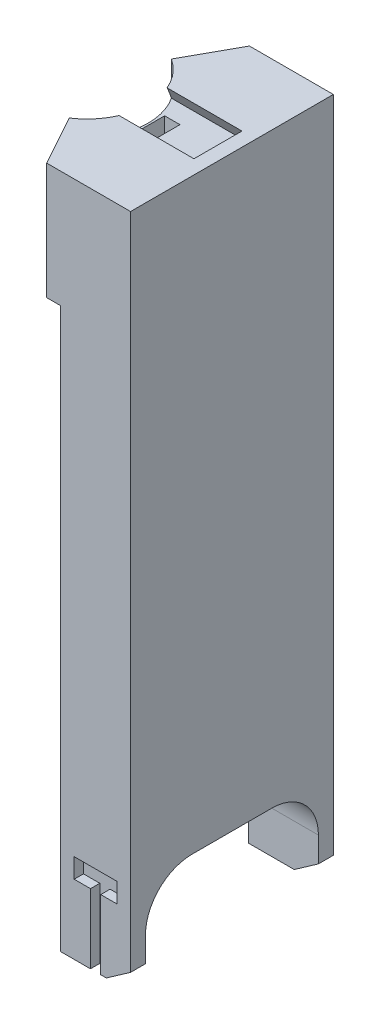
SolidWorks part; units mm, degrees
ref_plane "Front Plane" through (0, 0, 0) normal (0, 0, 1) x (1, 0, 0)
ref_plane "Top Plane" through (0, 0, 0) normal (0, 1, 0) x (1, 0, 0)
ref_plane "Right Plane" through (0, 0, 0) normal (1, 0, 0) x (0, 0, -1)
sketch "Sketch2" plane through (0, 0, 0) normal (0, 1, 0) x (1, 0, 0)
  line L0 (-9, 21.75) -> (-14.9513, 10.9504)
  line L1 (-9, -21.75) -> (9, -21.75)
  line L2 (-9, -21.75) -> (-9, 21.75)
  line L3 (-9, 21.75) -> (9, 21.75)
  line L4 (9, -21.75) -> (9, 21.75)
  line L5 (-9, -21.75) -> (9, 21.75) construction
  line L6 (-9, 21.75) -> (9, -21.75) construction
  line L7 (-9, -21.75) -> (-14.9513, -10.9504)
  circle A0 centre (-22.05, 0) radius 13.05
  point P0 (0, 0)
  dimension "D1" = 26.1
  dimension "D2" = 43.5
  dimension "D3" = 18
extrude "Boss-Extrude1" add sketch "Sketch2" along normal blind 25 contours A0 L2 L0 | A0 L7 L2 | L1 L4 L3 L2 region at (-10.8717, 0, -12.2283) region at (0, 0, 0) region at (-10.8717, 0, 12.2283)
ref_plane "Plane1" through (-9, 0, 0) normal (1, 0, 0) x (0, 0, -1)
sketch "Sketch3" plane through (-9, 0, 0) normal (1, 0, 0) x (0, 0, -1)
  line L0 (-5.15, 25) -> (5.15, 25)
  line L1 (5.15, 25) -> (7.15, 21.5359)
  line L2 (7.15, 21.5359) -> (-7.15, 21.5359)
  line L3 (-7.15, 21.5359) -> (-5.15, 25)
  line L4 (-21.75, 25) -> (21.75, 25) construction
  point P4 (0, 25)
  point P7 (0, 25)
  point P8 (0, 21.5359)
  dimension "D1" = 10.3
  dimension "D2" = 14.3
  dimension "D3" = 60
extrude "Cut-Extrude1" cut sketch "Sketch3" against normal through all and the other way blind 15
sketch "Sketch4" plane through (-9, 0, 0) normal (1, 0, 0) x (0, 0, -1)
  line L0 (0, 29.4041) -> (0, 4.5359) construction
  line L1 (3.15, 29.4041) -> (3.15, 4.5359)
  line L2 (-3.15, 29.4041) -> (-3.15, 4.5359)
  line L3 (7.15, 21.5359) -> (-7.15, 21.5359) construction
  arc A0 (3.15, 29.4041) -> (-3.15, 29.4041) centre (0, 29.4041) ccw
  arc A1 (-3.15, 4.5359) -> (3.15, 4.5359) centre (0, 4.5359) ccw
  point P3 (0, 16.97)
  dimension "D1" = 6.3
  dimension "D2" = 17
extrude "Cut-Extrude2" cut sketch "Sketch4" along normal blind 3.3 from offset 0.4
sketch "Sketch5" plane through (0, 0, 0) normal (0, -1, 0) x (1, 0, 0)
  line L0 (-9, -21.75) -> (9, -21.75) construction
  line L1 (9, 21.75) -> (-6, 21.75)
  line L2 (9, 21.75) -> (9, -21.75)
  line L3 (9, -21.75) -> (-6, -21.75)
  line L4 (-6, 21.75) -> (-6, -21.75)
  dimension "D1" = 15
extrude "Boss-Extrude2" add sketch "Sketch5" along normal blind 120
sketch "Sketch6" plane through (0, 0, 21.75) normal (0, 0, 1) x (1, 0, 0)
  line L1 (0.4, -105.1) -> (2.6, -105.1)
  line L2 (0.4, -105.1) -> (0.4, -120)
  line L3 (0.4, -120) -> (2.6, -120)
  line L4 (2.6, -105.1) -> (2.6, -120)
  line L5 (0.4, -105.1) -> (2.6, -120) construction
  line L6 (0.4, -120) -> (2.6, -105.1) construction
  line L7 (9, -120) -> (-6, -120) construction
  line L8 (-3.1, -100.9) -> (6.1, -100.9)
  line L9 (-3.1, -100.9) -> (-3.1, -105.1)
  line L10 (-3.1, -105.1) -> (6.1, -105.1)
  line L11 (6.1, -100.9) -> (6.1, -105.1)
  line L12 (-3.1, -100.9) -> (6.1, -105.1) construction
  line L13 (-3.1, -105.1) -> (6.1, -100.9) construction
  point P0 (1.5, -112.55)
  point P7 (1.5, -103)
  point P15 (1.5, -120)
  line M11 (-6, -120) -> (9, -120)
  dimension "D1" = 2.2
  dimension "D2" = 4.2
  dimension "D3" = 9.2
  dimension "D4" = 14.9
extrude "Cut-Extrude3" cut sketch "Sketch6" against normal blind 2 contours L11 L8 L9 L10 L1 | L4 L1 L2 M11 region at (1.5, -103, 21.75) region at (1.5, -112.55, 21.75)
extrude "Cut-Extrude4" cut sketch "Sketch6<3>" along normal blind 2 from surface contours L11 L8 L9 L10 L1 | L4 L1 L2 M11 region at (1.5, -103, 21.75) region at (1.5, -112.55, 21.75) starting at face at (-2, -31.6667, -21.75)
sketch "Sketch6<3>" plane through (0, 0, 21.75) normal (0, 0, 1) x (1, 0, 0) same geometry as "Sketch6"
sketch "Sketch7" plane through (0, 0, 21.75) normal (0, 0, 1) x (1, 0, 0)
  line L0 (9, -120) -> (2.6, -120) construction
  line L1 (9, 25) -> (9, -120) construction
  line L2 (2.6, -105.1) -> (2.6, -120) construction
  line L3 (2.6, -105.1) -> (6.1, -105.1) construction
  line L4 (3.8, -120) -> (9, -116.3589)
  line L5 (9, -116.3589) -> (9, -120)
  line L6 (9, -120) -> (3.8, -120)
  ellipse E0 centre (9, -120) end of major axis (9, -133.7) minor radius 5.2
  line M3 (2.6, -120) -> (9, -120)
  line M4 (9, -120) -> (9, 25)
  dimension "D1" = 1.2
  dimension "D2" = 1.2
  dimension "D3" = 35
extrude "Cut-Extrude5" cut sketch "Sketch7" against normal through all contours L4 M3 M4 region at (7.2667, -118.7863, 21.75)
sketch "Sketch8" plane through (-6, 0, 0) normal (-1, 0, 0) x (0, 0, 1)
  line L0 (21.75, -120) -> (-21.75, -120) construction
  line L1 (18.55, -101) -> (-18.55, -101)
  line L2 (18.55, -101) -> (18.55, -139)
  line L3 (18.55, -139) -> (-18.55, -139)
  line L4 (-18.55, -101) -> (-18.55, -139)
  line L5 (18.55, -101) -> (-18.55, -139) construction
  line L6 (18.55, -139) -> (-18.55, -101) construction
  line L7 (-21.75, -120) -> (-21.75, 0) construction
  point P0 (0, -120)
  dimension "D1" = 3.2
  dimension "D2" = 19
extrude "Cut-Extrude6" cut sketch "Sketch8" against normal through all
fillet "Fillet1" radius 10 2 edges at (1.5, -101, 18.55) (1.5, -101, -18.55)
